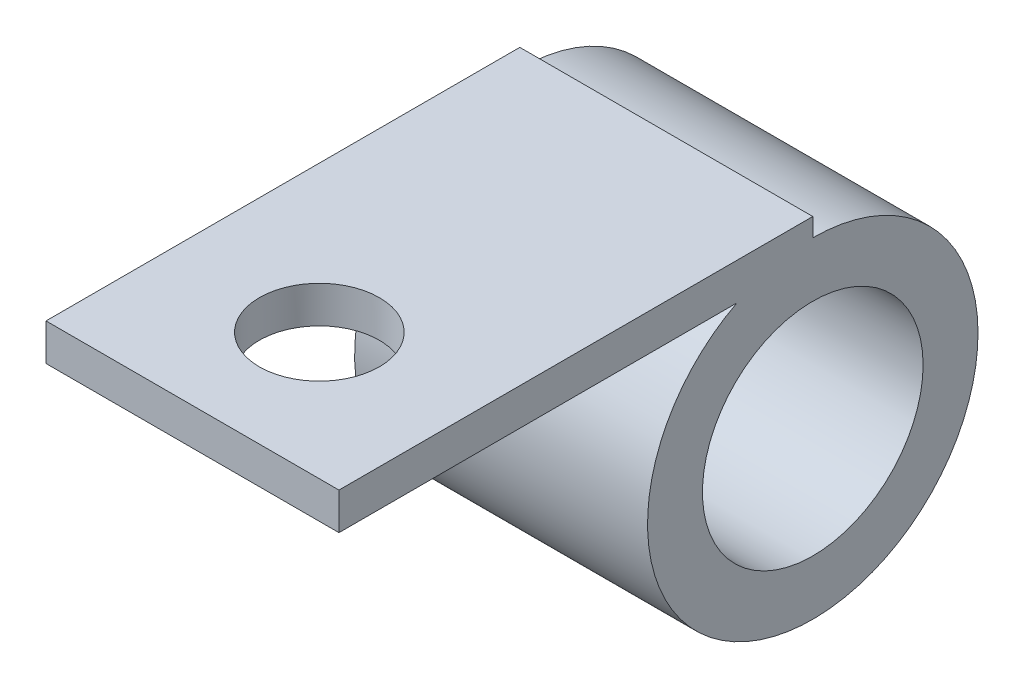
SolidWorks part; units mm, degrees
ref_plane "Front Plane" through (0, 0, 0) normal (0, 0, 1) x (1, 0, 0)
ref_plane "Top Plane" through (0, 0, 0) normal (0, 1, 0) x (1, 0, 0)
ref_plane "Right Plane" through (0, 0, 0) normal (1, 0, 0) x (0, 0, -1)
sketch "Loop Sketch" plane through (0, 0, 0) normal (1, 0, 0) x (0, 0, -1)
  circle A0 centre (0, 0) radius 7.1625
extrude "Loop" add sketch "Loop Sketch" along normal mid plane 12.7
ref_axis "Engine Axis" through (6.985, 0, 0) along (-1, 0, 0)
sketch "Tab Sketch" plane through (0, 0, 0) normal (1, 0, 0) x (0, 0, -1)
  line L0 (0, 6.3625) -> (-20.54, 6.3625)
  line L1 (-20.54, 6.3625) -> (-20.54, 7.9625)
  line L2 (-20.54, 7.9625) -> (0, 7.9625)
  line L3 (0, 7.9625) -> (0, 6.3625)
extrude "Tab" add sketch "Tab Sketch" along normal mid plane 12.7
sketch "Tube Hole Sketch" plane through (0, 0, 0) normal (1, 0, 0) x (0, 0, -1)
  circle A0 centre (0, 0) radius 4.7825
extrude "Tube Hole" cut sketch "Tube Hole Sketch" against normal mid plane 14.7
sketch "Mount Hole Sketch" plane through (0, 0, 0) normal (0, 1, 0) x (1, 0, 0)
  circle A0 centre (0, -15.04) radius 2.6
extrude "Mount Hole" cut sketch "Mount Hole Sketch" against normal mid plane 40
